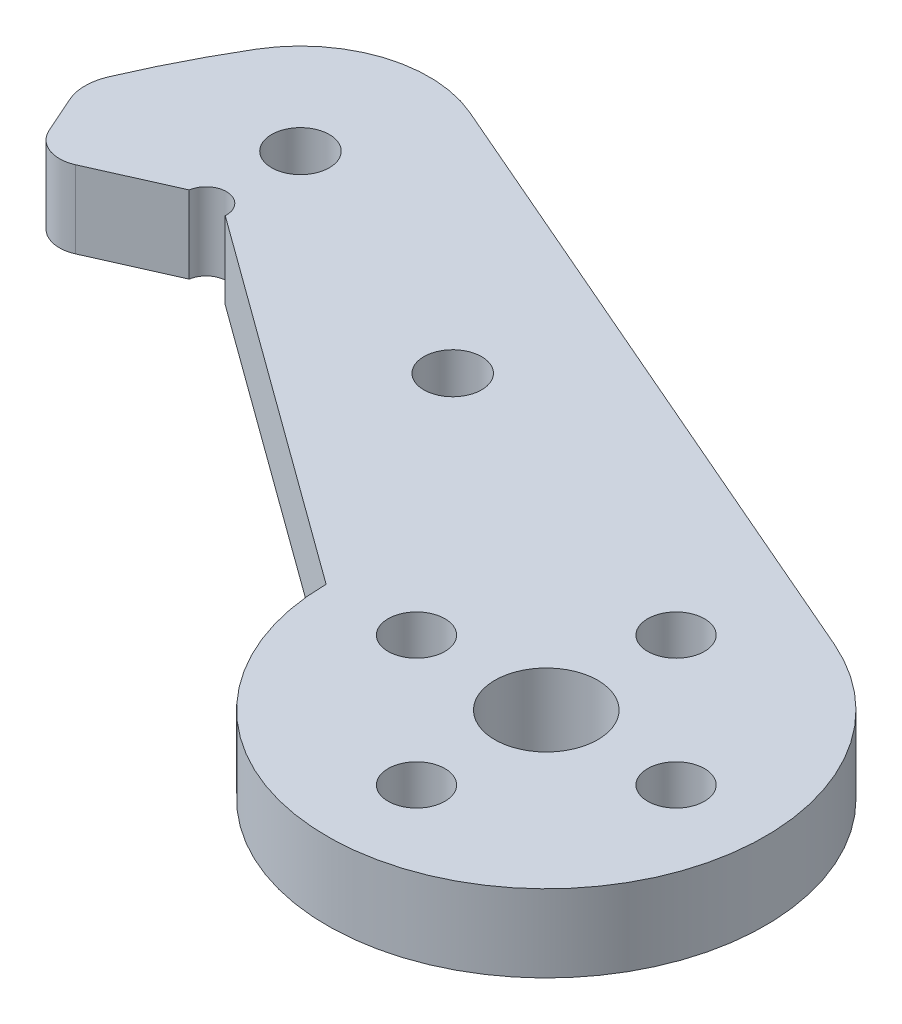
SolidWorks part; units mm, degrees
ref_plane "Front" through (0, 0, 0) normal (0, 0, 1) x (1, 0, 0)
ref_plane "Top" through (0, 0, 0) normal (0, 1, 0) x (1, 0, 0)
ref_plane "Right" through (0, 0, 0) normal (1, 0, 0) x (0, 0, -1)
ref_axis "side-side" through (80.9, 0, 0) along (-1, 0, 0)
ref_axis "up-down" through (0, 50, 0) along (0, -1, 0)
ref_axis "front-back" through (0, 0, -80.9) along (0, 0, 1)
sketch "Sketch1" plane through (0, 0, 0) normal (0, 1, 0) x (1, 0, 0)
  line L0 (-37.5348, 16.5677) -> (-37.4529, 17.3438) construction
  line L1 (-38.7702, 16.758) -> (-43.6254, 14.5987)
  line L2 (-36.2869, 16.4959) -> (-13.4998, -0.0747)
  line L3 (-46.2656, 15.6135) -> (-47.2827, 17.9005)
  line L4 (-31.9555, 16.4959) -> (-45.3508, 22.2593) construction
  line L5 (-34.2596, 29.5434) -> (5.3636, 12.3888)
  line L6 (-36.2869, 16.4959) -> (-38.7702, 16.758) construction
  arc A0 (-43.6254, 14.5987) -> (-46.2656, 15.6135) centre (-44.4381, 16.4262) cw
  arc A1 (-47.2983, 20.3029) -> (-44.2347, 26.3178) centre (0, 0) cw
  arc A2 (-47.2983, 20.3029) -> (-47.2827, 17.9005) centre (-44.5415, 19.1196) ccw
  arc A3 (-34.2596, 29.5434) -> (-44.2347, 26.3178) centre (-37.4133, 22.2593) ccw
  arc A4 (-38.7702, 16.758) -> (-36.2869, 16.4959) centre (-37.5348, 16.5677) cw
  arc A5 (-13.4998, -0.0747) -> (5.3636, 12.3888) centre (0, 0) ccw
  circle A6 centre (8, 0) radius 1.75 construction
  circle A7 centre (0, -8) radius 1.75 construction
  circle A8 centre (-8, 0) radius 1.75 construction
  circle A9 centre (0, 8) radius 1.75 construction
  circle A10 centre (8, 0) radius 1.75
  circle A11 centre (0, -8) radius 1.75
  circle A12 centre (-8, 0) radius 1.75
  circle A13 centre (0, 8) radius 1.75
  circle A14 centre (-37.4133, 22.2593) radius 7.9375 construction
  circle A15 centre (0, 0) radius 3.175
  circle A16 centre (-20.8625, 15.0937) radius 7.9375 construction
  circle A17 centre (-20.8625, 15.0937) radius 1.778
  circle A18 centre (-37.4133, 22.2593) radius 1.778
  point P0 (-37.4529, 17.3438)
  point P11 (-45.4529, 13.786)
  dimension "D2" = 3
  dimension "D4" = 27
  dimension "D5" = 51.4717
  dimension "D8" = 2
  dimension "D9" = 0.7804
  dimension "D7" = 1.25
  dimension "D11" = 15.875
  dimension "D13" = 6.35
  dimension "D14" = 3.556
  dimension "D1" = 8.7554
  dimension "D3" = 8
  dimension "D6" = 120
  dimension "D10" = 12.4641
  dimension "D12" = 25.75
extrude "Boss-Extrude1" add sketch "Sketch1" along normal blind 4.7625
